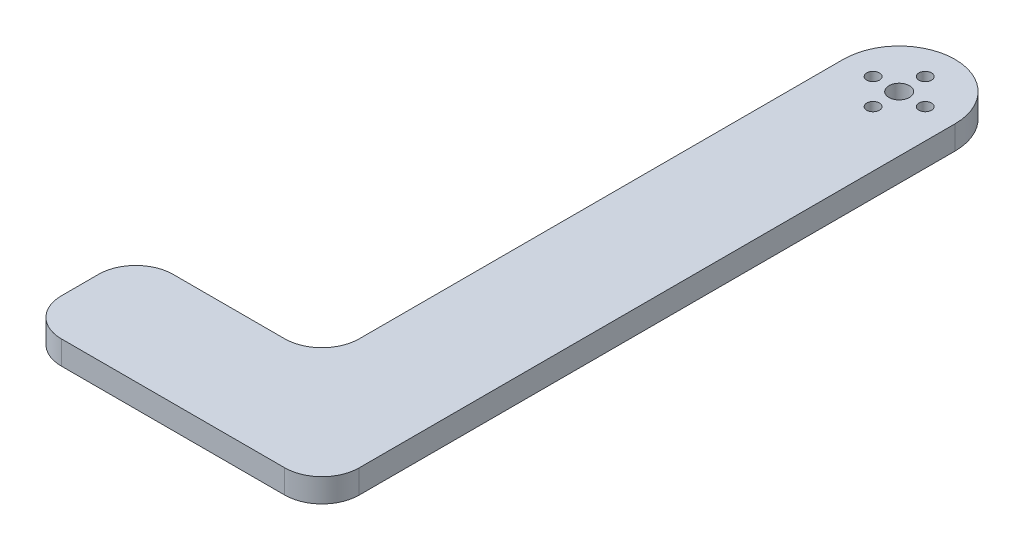
SolidWorks part; units mm, degrees
material "Pine"
ref_plane "Front Plane" through (0, 0, 0) normal (0, 0, 1) x (1, 0, 0)
ref_plane "Top Plane" through (0, 0, 0) normal (0, 1, 0) x (1, 0, 0)
ref_plane "Right Plane" through (0, 0, 0) normal (1, 0, 0) x (0, 0, -1)
sketch "Sketch2" plane through (0, 0, 0) normal (0, 1, 0) x (1, 0, 0)
  line L0 (-15, 0) -> (-15, -140)
  line L1 (-15, -140) -> (-65, -140)
  line L2 (-65, -140) -> (-65, -170)
  line L3 (-65, -170) -> (15, -170)
  line L4 (15, -170) -> (15, 0)
  circle A0 centre (0, 0) radius 15
  circle A1 centre (0, 0) radius 7 construction
  dimension "D1" = 30
  dimension "D2" = 14
  dimension "D3" = 30
  dimension "D4" = 50
  dimension "D5" = 170
extrude "Boss-Extrude1" add sketch "Sketch2" along normal blind 6.35 contours A0 L0 L1 L2 L3 L4 | A0 region at (-9.6053, 0, 106.2583) region at (0, 0, 0)
sketch "Sketch3" plane through (0, 6.35, 0) normal (0, 1, 0) x (1, 0, 0)
  circle A0 centre (0, 0) radius 7 construction
  circle A1 centre (0, 0) radius 7 construction
  point P3 (0, 7)
hole_wizard "M3 Clearance Hole1" positions "Sketch3" profile "Sketch4" hole size "M3" standard "ANSI Metric" end condition through all
sketch "Sketch4" plane through (0, 6.35, -7) normal (1, 0, 0) x (0, 0, 1)
  line L0 (0, 0) -> (0, 6.35)
  line L1 (0, 6.35) -> (1.7, 6.35)
  line L2 (1.7, 6.35) -> (1.7, 0)
  line L5 (1.7, 0) -> (0, 0)
  line L11 (0, -6.35) -> (0, 107.95) construction
  dimension "Thru Hole Dia." = 3.4
  dimension "Thru Hole Depth" = 6.35
pattern_circular "CirPattern1" count 4 over 360 about axis through (0, 6.35, 0) along (0, -1, 0) of "M3 Clearance Hole1" reverse direction yes
fillet "Fillet1" radius 10 4 edges at (15, 3.175, 170) (-65, 3.175, 170) (-65, 3.175, 140) (-15, 3.175, 140)
sketch "Sketch5" plane through (0, 6.35, 0) normal (0, 1, 0) x (1, 0, 0)
  circle A0 centre (0, 0) radius 2.75
  dimension "D1" = 5.5
extrude "Cut-Extrude1" cut sketch "Sketch5" against normal blind 10
